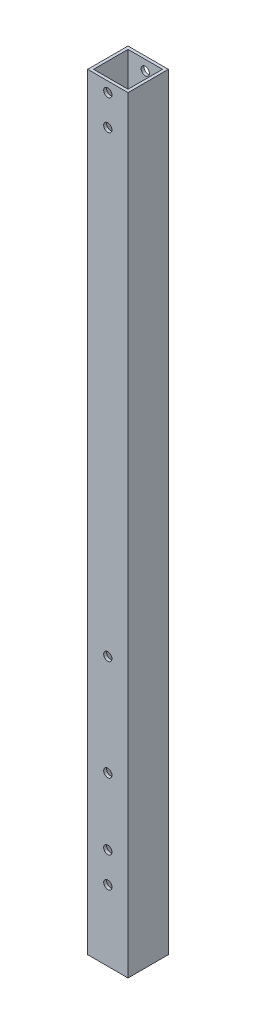
SolidWorks part; units mm, degrees
material "Thornel VCB-20 Carbon Cloth"
ref_plane "Front Plane" through (0, 0, 0) normal (0, 0, 1) x (1, 0, 0)
ref_plane "Top Plane" through (0, 0, 0) normal (0, 1, 0) x (1, 0, 0)
ref_plane "Right Plane" through (0, 0, 0) normal (1, 0, 0) x (0, 0, -1)
sketch "Sketch1" plane through (0, 0, 0) normal (0, 1, 0) x (1, 0, 0)
  line L0 (1.45, 18.55) -> (18.55, 18.55)
  line L1 (0, 0) -> (20, 0)
  line L2 (0, 0) -> (0, 20)
  line L3 (0, 20) -> (20, 20)
  line L4 (20, 0) -> (20, 20)
  line L5 (18.55, 1.45) -> (18.55, 18.55)
  line L6 (1.45, 1.45) -> (18.55, 1.45)
  line L7 (1.45, 1.45) -> (1.45, 18.55)
  dimension "D1" = 20
  dimension "D2" = 1.45
extrude "Boss-Extrude1" add sketch "Sketch1" along normal blind 350
sketch "Sketch2" plane through (0, 0, -20) normal (0, 0, -1) x (-1, 0, 0)
  line L0 (-20, 350) -> (0, 350) construction
  line L1 (-20, 350) -> (-20, 0) construction
  line L2 (-20, 0) -> (0, 0) construction
  circle A0 centre (-10, 345) radius 2.05
  circle A1 centre (-10, 330) radius 2.05
  circle A2 centre (-10, 20) radius 2.05
  circle A3 centre (-10, 5) radius 2.05
  dimension "D1" = 15
  dimension "D2" = 4.1
  dimension "D3" = 5
  dimension "D4" = 10
  dimension "D5" = 15
  dimension "D6" = 5
extrude "Cut-Extrude1" cut sketch "Sketch2" against normal through all
sketch "Sketch3" plane through (0, 0, -20) normal (0, 0, -1) x (-1, 0, 0)
  line L0 (-20, 0) -> (0, 0) construction
  line L1 (-20, 350) -> (0, 350) construction
  circle A0 centre (-10, 103) radius 2.05
  circle A1 centre (-10, 53) radius 2.05
  circle A2 centre (-10, 5) radius 2.05 construction
  point P4 (0, 0)
  point P7 (-10, 0)
  dimension "D1" = 50
  dimension "D2" = 247
extrude "Cut-Extrude2" cut sketch "Sketch3" against normal through all
sketch "Sketch4" plane through (0, 0, 0) normal (0, -1, 0) x (1, 0, 0)
  line L1 (0, 0) -> (20, 0)
  line L2 (0, 0) -> (0, -20)
  line L3 (0, -20) -> (20, -20)
  line L4 (20, 0) -> (20, -20)
  line L5 (18.55, -18.55) -> (1.45, -18.55)
  line L6 (18.55, -18.55) -> (18.55, -1.45)
  line L7 (18.55, -1.45) -> (1.45, -1.45)
  line L8 (1.45, -18.55) -> (1.45, -1.45)
extrude "Boss-Extrude2" add sketch "Sketch4" along normal blind 30
